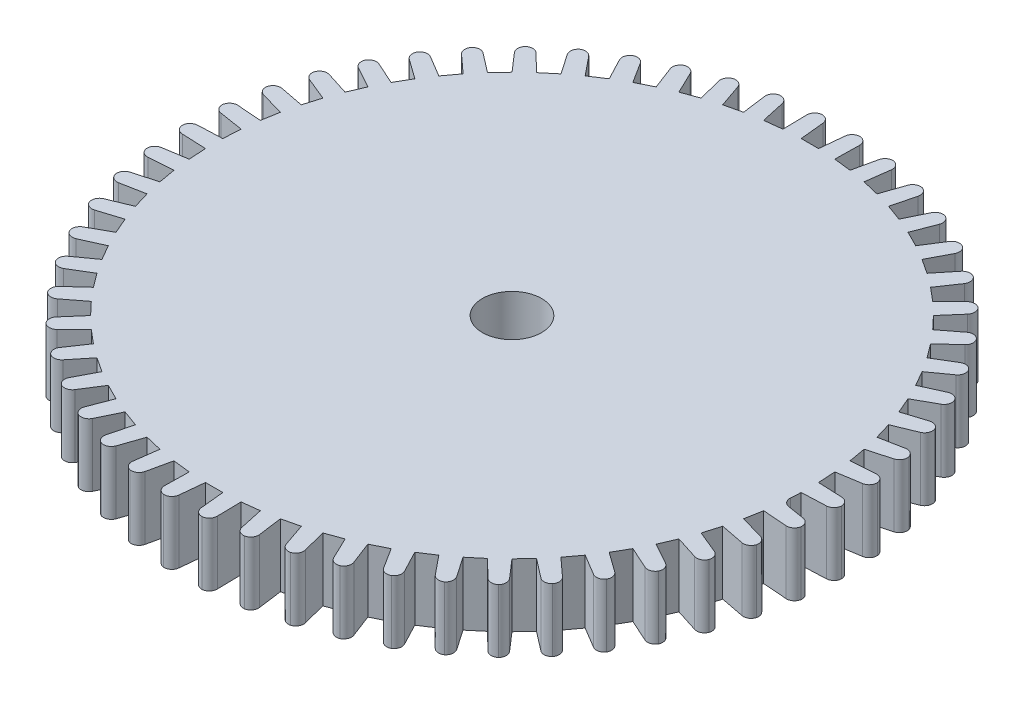
SolidWorks part; units mm, degrees
ref_plane "Front Plane" through (0, 0, 0) normal (0, 0, 1) x (1, 0, 0)
ref_plane "Top Plane" through (0, 0, 0) normal (0, 1, 0) x (1, 0, 0)
ref_plane "Right Plane" through (0, 0, 0) normal (1, 0, 0) x (0, 0, -1)
sketch "Sketch1" plane through (0, 0, 0) normal (0, 1, 0) x (1, 0, 0)
  line L0 (-0.22, 7.5446) -> (0.22, 7.5446)
  line L1 (0.22, 7.5446) -> (0.3, 8.3446)
  line L2 (-0.22, 7.5446) -> (-0.3, 8.3446)
  line L4 (0.6574, 7.5191) -> (0.6708, 8.323)
  line L5 (0.6574, 7.5191) -> (1.0944, 7.4681)
  line L6 (1.0944, 7.4681) -> (1.2667, 8.2534)
  line L7 (1.5258, 7.392) -> (1.6325, 8.1889)
  line L8 (1.5258, 7.392) -> (1.954, 7.2905)
  line L9 (1.954, 7.2905) -> (2.2163, 8.0505)
  line L10 (2.3737, 7.1649) -> (2.5721, 7.944)
  line L11 (2.3737, 7.1649) -> (2.7871, 7.0144)
  line L12 (2.7871, 7.0144) -> (3.1359, 7.7388)
  line L13 (3.1894, 6.8408) -> (3.477, 7.5917)
  line L14 (3.1894, 6.8408) -> (3.5826, 6.6434)
  line L15 (3.5826, 6.6434) -> (4.0131, 7.3224)
  line L16 (3.962, 6.4243) -> (4.3348, 7.1367)
  line L17 (3.962, 6.4243) -> (4.3296, 6.1825)
  line L18 (4.3296, 6.1825) -> (4.8361, 6.807)
  line L19 (4.6811, 5.9209) -> (5.134, 6.5852)
  line L20 (4.6811, 5.9209) -> (5.0181, 5.6381)
  line L21 (5.0181, 5.6381) -> (5.5936, 6.1995)
  line L22 (5.3368, 5.3374) -> (5.8638, 5.9446)
  line L23 (5.3368, 5.3374) -> (5.6387, 5.0174)
  line L24 (5.6387, 5.0174) -> (6.2755, 5.5082)
  line L25 (5.9203, 4.6818) -> (6.5143, 5.2237)
  line L26 (5.9203, 4.6818) -> (6.1831, 4.3289)
  line L27 (6.1831, 4.3289) -> (6.8726, 4.7424)
  line L28 (6.4238, 3.9628) -> (7.0766, 4.4321)
  line L29 (6.4238, 3.9628) -> (6.6438, 3.5818)
  line L30 (6.6438, 3.5818) -> (7.3766, 3.9125)
  line L31 (6.8404, 3.1903) -> (7.5433, 3.5806)
  line L32 (6.8404, 3.1903) -> (7.0147, 2.7863)
  line L33 (7.0147, 2.7863) -> (7.781, 3.0297)
  line L34 (7.1646, 2.3746) -> (7.908, 2.6807)
  line L35 (7.1646, 2.3746) -> (7.2908, 1.9531)
  line L36 (7.2908, 1.9531) -> (8.0801, 2.1059)
  line L37 (7.3918, 1.5268) -> (8.1657, 1.7445)
  line L38 (7.3918, 1.5268) -> (7.4682, 1.0934)
  line L39 (7.4682, 1.0934) -> (8.2699, 1.1536)
  line L40 (7.5191, 0.6583) -> (8.313, 0.7847)
  line L41 (7.5191, 0.6583) -> (7.5446, 0.2191)
  line L42 (7.5446, 0.2191) -> (8.3479, 0.1857)
  line L43 (7.5446, -0.2191) -> (8.3479, -0.1857)
  line L44 (7.5446, -0.2191) -> (7.5191, -0.6583)
  line L45 (7.5191, -0.6583) -> (8.313, -0.7847)
  line L46 (7.4682, -1.0934) -> (8.2699, -1.1536)
  line L47 (7.4682, -1.0934) -> (7.3918, -1.5268)
  line L48 (7.3918, -1.5268) -> (8.1657, -1.7445)
  line L49 (7.2908, -1.9531) -> (8.0801, -2.1059)
  line L50 (7.2908, -1.9531) -> (7.1646, -2.3746)
  line L51 (7.1646, -2.3746) -> (7.908, -2.6807)
  line L52 (7.0147, -2.7863) -> (7.781, -3.0297)
  line L53 (7.0147, -2.7863) -> (6.8404, -3.1903)
  line L54 (6.8404, -3.1903) -> (7.5433, -3.5806)
  line L55 (6.6438, -3.5818) -> (7.3766, -3.9125)
  line L56 (6.6438, -3.5818) -> (6.4238, -3.9628)
  line L57 (6.4238, -3.9628) -> (7.0766, -4.4321)
  line L58 (6.1831, -4.3289) -> (6.8726, -4.7424)
  line L59 (6.1831, -4.3289) -> (5.9203, -4.6818)
  line L60 (5.9203, -4.6818) -> (6.5143, -5.2237)
  line L61 (5.6387, -5.0174) -> (6.2755, -5.5082)
  line L62 (5.6387, -5.0174) -> (5.3368, -5.3374)
  line L63 (5.3368, -5.3374) -> (5.8638, -5.9446)
  line L64 (5.0181, -5.6381) -> (5.5936, -6.1995)
  line L65 (5.0181, -5.6381) -> (4.6811, -5.9209)
  line L66 (4.6811, -5.9209) -> (5.134, -6.5852)
  line L67 (4.3296, -6.1825) -> (4.8361, -6.807)
  line L68 (4.3296, -6.1825) -> (3.962, -6.4243)
  line L69 (3.962, -6.4243) -> (4.3348, -7.1367)
  line L70 (3.5826, -6.6434) -> (4.0131, -7.3224)
  line L71 (3.5826, -6.6434) -> (3.1894, -6.8408)
  line L72 (3.1894, -6.8408) -> (3.477, -7.5917)
  line L73 (2.7871, -7.0144) -> (3.1359, -7.7388)
  line L74 (2.7871, -7.0144) -> (2.3737, -7.1649)
  line L75 (2.3737, -7.1649) -> (2.5721, -7.944)
  line L76 (1.954, -7.2905) -> (2.2163, -8.0505)
  line L77 (1.954, -7.2905) -> (1.5258, -7.392)
  line L78 (1.5258, -7.392) -> (1.6325, -8.1889)
  line L79 (1.0944, -7.4681) -> (1.2667, -8.2534)
  line L80 (1.0944, -7.4681) -> (0.6574, -7.5191)
  line L81 (0.6574, -7.5191) -> (0.6708, -8.323)
  line L82 (0.22, -7.5446) -> (0.3, -8.3446)
  line L83 (0.22, -7.5446) -> (-0.22, -7.5446)
  line L84 (-0.22, -7.5446) -> (-0.3, -8.3446)
  line L85 (-0.6574, -7.5191) -> (-0.6708, -8.323)
  line L86 (-0.6574, -7.5191) -> (-1.0944, -7.4681)
  line L87 (-1.0944, -7.4681) -> (-1.2667, -8.2534)
  line L88 (-1.5258, -7.392) -> (-1.6325, -8.1889)
  line L89 (-1.5258, -7.392) -> (-1.954, -7.2905)
  line L90 (-1.954, -7.2905) -> (-2.2163, -8.0505)
  line L91 (-2.3737, -7.1649) -> (-2.5721, -7.944)
  line L92 (-2.3737, -7.1649) -> (-2.7871, -7.0144)
  line L93 (-2.7871, -7.0144) -> (-3.1359, -7.7388)
  line L94 (-3.1894, -6.8408) -> (-3.477, -7.5917)
  line L95 (-3.1894, -6.8408) -> (-3.5826, -6.6434)
  line L96 (-3.5826, -6.6434) -> (-4.0131, -7.3224)
  line L97 (-3.962, -6.4243) -> (-4.3348, -7.1367)
  line L98 (-3.962, -6.4243) -> (-4.3296, -6.1825)
  line L99 (-4.3296, -6.1825) -> (-4.8361, -6.807)
  line L100 (-4.6811, -5.9209) -> (-5.134, -6.5852)
  line L101 (-4.6811, -5.9209) -> (-5.0181, -5.6381)
  line L102 (-5.0181, -5.6381) -> (-5.5936, -6.1995)
  line L103 (-5.3368, -5.3374) -> (-5.8638, -5.9446)
  line L104 (-5.3368, -5.3374) -> (-5.6387, -5.0174)
  line L105 (-5.6387, -5.0174) -> (-6.2755, -5.5082)
  line L106 (-5.9203, -4.6818) -> (-6.5143, -5.2237)
  line L107 (-5.9203, -4.6818) -> (-6.1831, -4.3289)
  line L108 (-6.1831, -4.3289) -> (-6.8726, -4.7424)
  line L109 (-6.4238, -3.9628) -> (-7.0766, -4.4321)
  line L110 (-6.4238, -3.9628) -> (-6.6438, -3.5818)
  line L111 (-6.6438, -3.5818) -> (-7.3766, -3.9125)
  line L112 (-6.8404, -3.1903) -> (-7.5433, -3.5806)
  line L113 (-6.8404, -3.1903) -> (-7.0147, -2.7863)
  line L114 (-7.0147, -2.7863) -> (-7.781, -3.0297)
  line L115 (-7.1646, -2.3746) -> (-7.908, -2.6807)
  line L116 (-7.1646, -2.3746) -> (-7.2908, -1.9531)
  line L117 (-7.2908, -1.9531) -> (-8.0801, -2.1059)
  line L118 (-7.3918, -1.5268) -> (-8.1657, -1.7445)
  line L119 (-7.3918, -1.5268) -> (-7.4682, -1.0934)
  line L120 (-7.4682, -1.0934) -> (-8.2699, -1.1536)
  line L121 (-7.5191, -0.6583) -> (-8.313, -0.7847)
  line L122 (-7.5191, -0.6583) -> (-7.5446, -0.2191)
  line L123 (-7.5446, -0.2191) -> (-8.3479, -0.1857)
  line L124 (-7.5446, 0.2191) -> (-8.3479, 0.1857)
  line L125 (-7.5446, 0.2191) -> (-7.5191, 0.6583)
  line L126 (-7.5191, 0.6583) -> (-8.313, 0.7847)
  line L127 (-7.4682, 1.0934) -> (-8.2699, 1.1536)
  line L128 (-7.4682, 1.0934) -> (-7.3918, 1.5268)
  line L129 (-7.3918, 1.5268) -> (-8.1657, 1.7445)
  line L130 (-7.2908, 1.9531) -> (-8.0801, 2.1059)
  line L131 (-7.2908, 1.9531) -> (-7.1646, 2.3746)
  line L132 (-7.1646, 2.3746) -> (-7.908, 2.6807)
  line L133 (-7.0147, 2.7863) -> (-7.781, 3.0297)
  line L134 (-7.0147, 2.7863) -> (-6.8404, 3.1903)
  line L135 (-6.8404, 3.1903) -> (-7.5433, 3.5806)
  line L136 (-6.6438, 3.5818) -> (-7.3766, 3.9125)
  line L137 (-6.6438, 3.5818) -> (-6.4238, 3.9628)
  line L138 (-6.4238, 3.9628) -> (-7.0766, 4.4321)
  line L139 (-6.1831, 4.3289) -> (-6.8726, 4.7424)
  line L140 (-6.1831, 4.3289) -> (-5.9203, 4.6818)
  line L141 (-5.9203, 4.6818) -> (-6.5143, 5.2237)
  line L142 (-5.6387, 5.0174) -> (-6.2755, 5.5082)
  line L143 (-5.6387, 5.0174) -> (-5.3368, 5.3374)
  line L144 (-5.3368, 5.3374) -> (-5.8638, 5.9446)
  line L145 (-5.0181, 5.6381) -> (-5.5936, 6.1995)
  line L146 (-5.0181, 5.6381) -> (-4.6811, 5.9209)
  line L147 (-4.6811, 5.9209) -> (-5.134, 6.5852)
  line L148 (-4.3296, 6.1825) -> (-4.8361, 6.807)
  line L149 (-4.3296, 6.1825) -> (-3.962, 6.4243)
  line L150 (-3.962, 6.4243) -> (-4.3348, 7.1367)
  line L151 (-3.5826, 6.6434) -> (-4.0131, 7.3224)
  line L152 (-3.5826, 6.6434) -> (-3.1894, 6.8408)
  line L153 (-3.1894, 6.8408) -> (-3.477, 7.5917)
  line L154 (-2.7871, 7.0144) -> (-3.1359, 7.7388)
  line L155 (-2.7871, 7.0144) -> (-2.3737, 7.1649)
  line L156 (-2.3737, 7.1649) -> (-2.5721, 7.944)
  line L157 (-1.954, 7.2905) -> (-2.2163, 8.0505)
  line L158 (-1.954, 7.2905) -> (-1.5258, 7.392)
  line L159 (-1.5258, 7.392) -> (-1.6325, 8.1889)
  line L160 (-1.0944, 7.4681) -> (-1.2667, 8.2534)
  line L161 (-1.0944, 7.4681) -> (-0.6574, 7.5191)
  line L162 (-0.6574, 7.5191) -> (-0.6708, 8.323)
  circle A0 centre (0, 0) radius 0.75
  arc A1 (6.5143, 5.2237) -> (6.2755, 5.5082) centre (0, 0) ccw
  arc A2 (7.0766, 4.4321) -> (6.8726, 4.7424) centre (0, 0) ccw
  arc A3 (7.5433, 3.5806) -> (7.3766, 3.9125) centre (0, 0) ccw
  arc A4 (7.908, 2.6807) -> (7.781, 3.0297) centre (0, 0) ccw
  arc A5 (8.1657, 1.7445) -> (8.0801, 2.1059) centre (0, 0) ccw
  arc A6 (8.313, 0.7847) -> (8.2699, 1.1536) centre (0, 0) ccw
  arc A7 (8.3479, -0.1857) -> (8.3479, 0.1857) centre (0, 0) ccw
  arc A8 (8.2699, -1.1536) -> (8.313, -0.7847) centre (0, 0) ccw
  arc A9 (8.0801, -2.1059) -> (8.1657, -1.7445) centre (0, 0) ccw
  arc A10 (7.781, -3.0297) -> (7.908, -2.6807) centre (0, 0) ccw
  arc A11 (7.3766, -3.9125) -> (7.5433, -3.5806) centre (0, 0) ccw
  arc A12 (6.8726, -4.7424) -> (7.0766, -4.4321) centre (0, 0) ccw
  arc A13 (6.2755, -5.5082) -> (6.5143, -5.2237) centre (0, 0) ccw
  arc A14 (5.5936, -6.1995) -> (5.8638, -5.9446) centre (0, 0) ccw
  arc A15 (4.8361, -6.807) -> (5.134, -6.5852) centre (0, 0) ccw
  arc A16 (4.0131, -7.3224) -> (4.3348, -7.1367) centre (0, 0) ccw
  arc A17 (3.1359, -7.7388) -> (3.477, -7.5917) centre (0, 0) ccw
  arc A18 (2.2163, -8.0505) -> (2.5721, -7.944) centre (0, 0) ccw
  arc A19 (1.2667, -8.2534) -> (1.6325, -8.1889) centre (0, 0) ccw
  arc A20 (0.3, -8.3446) -> (0.6708, -8.323) centre (0, 0) ccw
  arc A21 (-0.6708, -8.323) -> (-0.3, -8.3446) centre (0, 0) ccw
  arc A22 (-1.6325, -8.1889) -> (-1.2667, -8.2534) centre (0, 0) ccw
  arc A23 (-2.5721, -7.944) -> (-2.2163, -8.0505) centre (0, 0) ccw
  arc A24 (-3.477, -7.5917) -> (-3.1359, -7.7388) centre (0, 0) ccw
  arc A25 (-4.3348, -7.1367) -> (-4.0131, -7.3224) centre (0, 0) ccw
  arc A26 (-5.134, -6.5852) -> (-4.8361, -6.807) centre (0, 0) ccw
  arc A27 (-5.8638, -5.9446) -> (-5.5936, -6.1995) centre (0, 0) ccw
  arc A28 (-6.5143, -5.2237) -> (-6.2755, -5.5082) centre (0, 0) ccw
  arc A29 (-7.0766, -4.4321) -> (-6.8726, -4.7424) centre (0, 0) ccw
  arc A30 (-7.5433, -3.5806) -> (-7.3766, -3.9125) centre (0, 0) ccw
  arc A31 (-7.908, -2.6807) -> (-7.781, -3.0297) centre (0, 0) ccw
  arc A32 (-8.1657, -1.7445) -> (-8.0801, -2.1059) centre (0, 0) ccw
  arc A33 (-8.313, -0.7847) -> (-8.2699, -1.1536) centre (0, 0) ccw
  arc A34 (-8.3479, 0.1857) -> (-8.3479, -0.1857) centre (0, 0) ccw
  arc A35 (-8.2699, 1.1536) -> (-8.313, 0.7847) centre (0, 0) ccw
  arc A36 (-8.0801, 2.1059) -> (-8.1657, 1.7445) centre (0, 0) ccw
  arc A37 (-7.781, 3.0297) -> (-7.908, 2.6807) centre (0, 0) ccw
  arc A38 (-7.3766, 3.9125) -> (-7.5433, 3.5806) centre (0, 0) ccw
  arc A39 (-6.8726, 4.7424) -> (-7.0766, 4.4321) centre (0, 0) ccw
  arc A40 (-6.2755, 5.5082) -> (-6.5143, 5.2237) centre (0, 0) ccw
  arc A41 (-5.5936, 6.1995) -> (-5.8638, 5.9446) centre (0, 0) ccw
  arc A42 (-4.8361, 6.807) -> (-5.134, 6.5852) centre (0, 0) ccw
  arc A43 (-4.0131, 7.3224) -> (-4.3348, 7.1367) centre (0, 0) ccw
  arc A44 (-3.1359, 7.7388) -> (-3.477, 7.5917) centre (0, 0) ccw
  arc A45 (-2.2163, 8.0505) -> (-2.5721, 7.944) centre (0, 0) ccw
  arc A46 (-1.2667, 8.2534) -> (-1.6325, 8.1889) centre (0, 0) ccw
  arc A47 (-0.3, 8.3446) -> (-0.6708, 8.323) centre (0, 0) ccw
  arc A48 (0.6708, 8.323) -> (0.3, 8.3446) centre (0, 0) ccw
  arc A49 (1.6325, 8.1889) -> (1.2667, 8.2534) centre (0, 0) ccw
  arc A50 (2.5721, 7.944) -> (2.2163, 8.0505) centre (0, 0) ccw
  arc A51 (3.477, 7.5917) -> (3.1359, 7.7388) centre (0, 0) ccw
  arc A52 (5.134, 6.5852) -> (4.8361, 6.807) centre (0, 0) ccw
  arc A53 (4.3348, 7.1367) -> (4.0131, 7.3224) centre (0, 0) ccw
  arc A54 (5.8638, 5.9446) -> (5.5936, 6.1995) centre (0, 0) ccw
  point P222 (0, 0)
  dimension "D1" = 1.5
  dimension "D2" = 16.7
  dimension "D3" = 0.6
  dimension "D4" = 0.44
  dimension "D6" = 54
extrude "Boss-Extrude1" add sketch "Sketch1" along normal blind 1.6
fillet "Fillet2" radius 0.2 2 edges at (4.3348, 0.8, 7.1367) (4.0131, 0.8, 7.3224)
fillet "Fillet3" radius 0.2 33 edges at (5.8638, 0.8, -5.9446) (5.5936, 0.8, -6.1995) (6.5143, 0.8, -5.2237) (6.2755, 0.8, -5.5082) (7.0766, 0.8, -4.4321) (6.8726, 0.8, -4.7424) (7.5433, 0.8, -3.5806) (7.3766, 0.8, -3.9125) (7.5191, 0.8, 0.6583) (7.908, 0.8, -2.6807) (7.781, 0.8, -3.0297) (8.0801, 0.8, -2.1059) (8.1657, 0.8, -1.7445) (8.2699, 0.8, -1.1536) (8.313, 0.8, -0.7847) (8.3479, 0.8, -0.1857) (8.3479, 0.8, 0.1857) (8.313, 0.8, 0.7847) (8.2699, 0.8, 1.1536) (8.0801, 0.8, 2.1059) (8.1657, 0.8, 1.7445) (7.908, 0.8, 2.6807) (7.781, 0.8, 3.0297) (7.5433, 0.8, 3.5806) (7.3766, 0.8, 3.9125) (6.8726, 0.8, 4.7424) (7.0766, 0.8, 4.4321) (6.2755, 0.8, 5.5082) (6.5143, 0.8, 5.2237) (5.8638, 0.8, 5.9446) (5.5936, 0.8, 6.1995) (5.134, 0.8, 6.5852) (4.8361, 0.8, 6.807)
fillet "Fillet4" radius 0.2 60 edges at (-4.3348, 0.8, 7.1367) (-4.0131, 0.8, 7.3224) (-3.477, 0.8, 7.5917) (-3.1359, 0.8, 7.7388) (-5.134, 0.8, 6.5852) (-4.8361, 0.8, 6.807) (-5.8638, 0.8, 5.9446) (-5.5936, 0.8, 6.1995) (-6.5143, 0.8, 5.2237) (-6.2755, 0.8, 5.5082) (-7.0766, 0.8, 4.4321) (-6.8726, 0.8, 4.7424) (-7.5433, 0.8, 3.5806) (-7.3766, 0.8, 3.9125) (-7.908, 0.8, 2.6807) (-7.781, 0.8, 3.0297) (-8.1657, 0.8, 1.7445) (-8.0801, 0.8, 2.1059) (-8.313, 0.8, 0.7847) (-8.2699, 0.8, 1.1536) (-8.3479, 0.8, -0.1857) (-8.3479, 0.8, 0.1857) (-8.2699, 0.8, -1.1536) (-8.313, 0.8, -0.7847) (-8.0801, 0.8, -2.1059) (-8.1657, 0.8, -1.7445) (-7.781, 0.8, -3.0297) (-7.908, 0.8, -2.6807) (-7.3766, 0.8, -3.9125) (-7.5433, 0.8, -3.5806) (-6.8726, 0.8, -4.7424) (-7.0766, 0.8, -4.4321) (-5.5936, 0.8, -6.1995) (-5.8638, 0.8, -5.9446) (-6.2755, 0.8, -5.5082) (-6.5143, 0.8, -5.2237) (-4.8361, 0.8, -6.807) (-5.134, 0.8, -6.5852) (-4.0131, 0.8, -7.3224) (-4.3348, 0.8, -7.1367) (-3.1359, 0.8, -7.7388) (-3.477, 0.8, -7.5917) (-1.2667, 0.8, -8.2534) (-1.6325, 0.8, -8.1889) (-2.2163, 0.8, -8.0505) (-2.5721, 0.8, -7.944) (-0.3, 0.8, -8.3446) (-0.6708, 0.8, -8.323) (0.6708, 0.8, -8.323) (0.3, 0.8, -8.3446) (1.6325, 0.8, -8.1889) (1.2667, 0.8, -8.2534) (2.5721, 0.8, -7.944) (2.2163, 0.8, -8.0505) (3.477, 0.8, -7.5917) (3.1359, 0.8, -7.7388) (4.3348, 0.8, -7.1367) (4.0131, 0.8, -7.3224) (5.134, 0.8, -6.5852) (4.8361, 0.8, -6.807)
fillet "Fillet5" radius 0.2 14 edges at (-2.2163, 0.8, 8.0505) (-2.5721, 0.8, 7.944) (-1.2667, 0.8, 8.2534) (-1.6325, 0.8, 8.1889) (-0.3, 0.8, 8.3446) (-0.6708, 0.8, 8.323) (0.3, 0.8, 8.3446) (0.6708, 0.8, 8.323) (1.2667, 0.8, 8.2534) (1.6325, 0.8, 8.1889) (2.2163, 0.8, 8.0505) (2.5721, 0.8, 7.944) (3.1359, 0.8, 7.7388) (3.477, 0.8, 7.5917)
